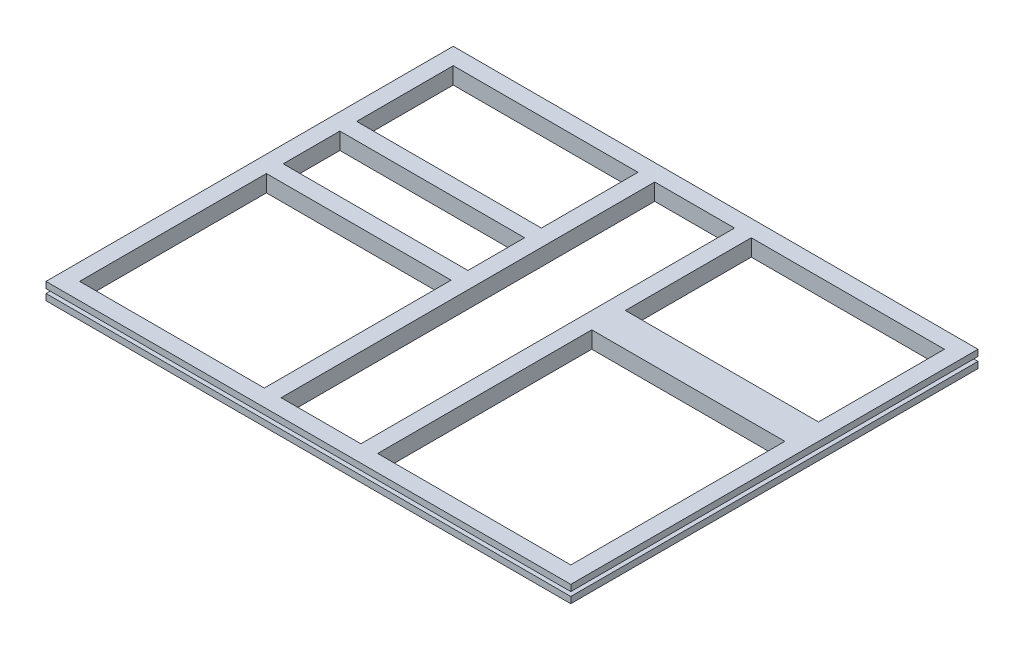
SolidWorks part; units mm, degrees
ref_plane "Front Plane" through (0, 0, 0) normal (0, 0, 1) x (1, 0, 0)
ref_plane "Top Plane" through (0, 0, 0) normal (0, 1, 0) x (1, 0, 0)
ref_plane "Right Plane" through (0, 0, 0) normal (1, 0, 0) x (0, 0, -1)
sketch "Sketch1" plane through (0, 0, 0) normal (0, 1, 0) x (1, 0, 0)
  line L0 (124.2721, 445) -> (124.2721, 145)
  line L1 (624.2721, -485) -> (-625.7279, -485)
  line L2 (624.2721, -485) -> (624.2721, 485)
  line L3 (624.2721, 485) -> (-625.7279, 485)
  line L4 (-625.7279, -485) -> (-625.7279, 485)
  line L5 (-145.7279, 0) -> (-145.7279, -445)
  line L6 (124.2721, 65) -> (124.2721, -445)
  line L7 (584.2721, -445) -> (124.2721, -445)
  line L8 (584.2721, -445) -> (584.2721, 65)
  line L9 (584.2721, 445) -> (124.2721, 445)
  line L10 (-585.7279, -445) -> (-585.7279, 0)
  line L11 (-145.7279, 175) -> (-145.7279, 40)
  line L12 (-145.7279, 445) -> (-585.7279, 445)
  line L13 (84.2721, 445) -> (84.2721, -445)
  line L14 (-105.7279, 445) -> (-105.7279, -445)
  line L15 (-145.7279, 445) -> (-145.7279, 215)
  line L16 (584.2721, 145) -> (124.2721, 145)
  line L17 (584.2721, 65) -> (124.2721, 65)
  line L18 (-145.7279, 215) -> (-585.7279, 215)
  line L19 (-145.7279, 175) -> (-585.7279, 175)
  line L20 (-145.7279, 40) -> (-585.7279, 40)
  line L21 (-145.7279, 0) -> (-585.7279, 0)
  line L22 (84.2721, 445) -> (-105.7279, 445)
  line L23 (-145.7279, -445) -> (-585.7279, -445)
  line L24 (84.2721, -445) -> (-105.7279, -445)
  line L25 (-585.7279, 40) -> (-585.7279, 175)
  line L26 (-585.7279, 215) -> (-585.7279, 445)
  line L27 (584.2721, 145) -> (584.2721, 445)
  point P0 (0, 0)
  point P6 (0, 0)
  dimension "D1" = 970
  dimension "D2" = 1250
  dimension "D3" = 40
  dimension "D4" = 40
  dimension "D5" = 40
  dimension "D6" = 40
  dimension "D7" = 460
  dimension "D8" = 480
  dimension "D9" = 270
  dimension "D10" = 310
  dimension "D11" = 40
  dimension "D12" = 445
  dimension "D13" = 80
  dimension "D14" = 340
extrude "Boss-Extrude1" add sketch "Sketch1" along normal blind 40
sketch "Sketch2" plane through (0, 0, 485) normal (0, 0, 1) x (1, 0, 0)
  line L0 (-625.7279, 40) -> (-625.7279, 0) construction
  line L1 (-625.7279, 25) -> (-615.7279, 25)
  line L2 (-625.7279, 25) -> (-625.7279, 15)
  line L3 (-625.7279, 15) -> (-615.7279, 15)
  line L4 (-615.7279, 25) -> (-615.7279, 15)
  line L5 (-625.7279, 25) -> (-615.7279, 15) construction
  line L6 (-625.7279, 15) -> (-615.7279, 25) construction
  line L7 (-625.7279, 40) -> (624.2721, 40) construction
  line L8 (614.2721, 25) -> (624.2721, 25)
  line L9 (614.2721, 25) -> (614.2721, 15)
  line L10 (614.2721, 15) -> (624.2721, 15)
  line L11 (624.2721, 25) -> (624.2721, 15)
  line L12 (624.2721, 40) -> (624.2721, 0) construction
  point P0 (-620.7279, 20)
  point P14 (624.2721, 20)
  dimension "D1" = 10
  dimension "D2" = 20
  dimension "D3" = 20
extrude "Cut-Extrude1" cut sketch "Sketch2" against normal through all both and the other way through all
sketch "Sketch3" plane through (-625.7279, 0, 0) normal (-1, 0, 0) x (0, 0, 1)
  line L0 (-485, 40) -> (485, 40) construction
  line L1 (475, 25) -> (485, 25)
  line L2 (475, 25) -> (475, 15)
  line L3 (475, 15) -> (485, 15)
  line L4 (485, 25) -> (485, 15)
  line L5 (475, 25) -> (485, 15) construction
  line L6 (475, 15) -> (485, 25) construction
  line L7 (485, 25) -> (485, 15) construction
  line L8 (-485, 15) -> (-485, 25) construction
  line L9 (-475, 15) -> (-485, 15)
  line L10 (-475, 15) -> (-475, 25)
  line L11 (-475, 25) -> (-485, 25)
  line L12 (-485, 15) -> (-485, 25)
  line L13 (-475, 15) -> (-485, 25) construction
  line L14 (-475, 25) -> (-485, 15) construction
  point P0 (480, 20)
  point P10 (-480, 20)
  dimension "D1" = 10
  dimension "D2" = 10
  dimension "D3" = 20
  dimension "D4" = 10
  dimension "D5" = 10
  dimension "D6" = 20
extrude "Cut-Extrude2" cut sketch "Sketch3" against normal through all both
